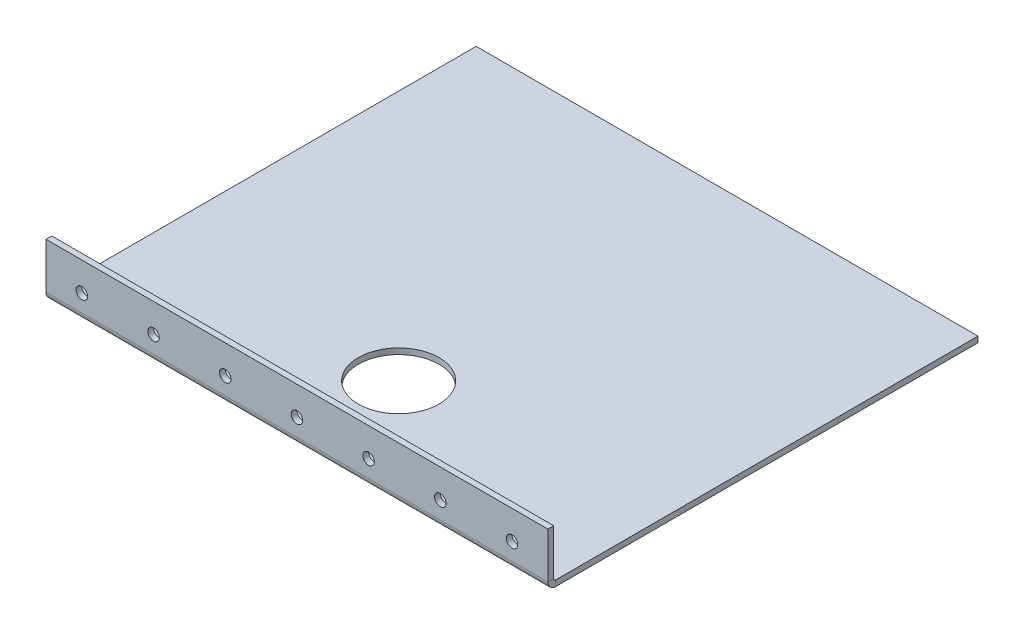
SolidWorks part; units mm, degrees
note: The reader was unsure of these and kept them because the rebuilt part matched: flange length of "Edge-Flange1".
ref_plane "Front Plane" through (0, 0, 0) normal (0, 0, 1) x (1, 0, 0)
ref_plane "Top Plane" through (0, 0, 0) normal (0, 1, 0) x (1, 0, 0)
ref_plane "Right Plane" through (0, 0, 0) normal (1, 0, 0) x (0, 0, -1)
sketch "Sketch1" plane through (0, 0, 0) normal (0, 1, 0) x (1, 0, 0)
  line L1 (-5638.8, 2754.0857) -> (-5461, 2754.0857)
  line L2 (-5638.8, 2754.0857) -> (-5638.8, 2601.6857)
  line L3 (-5638.8, 2601.6857) -> (-5461, 2601.6857)
  line L4 (-5461, 2754.0857) -> (-5461, 2601.6857)
  dimension "D1" = 152.4
  dimension "D2" = 177.8
base flange "Base-Flange1" sketch "Sketch1" thickness 2.0523 reverse thickness direction no parameters "D1"=0.7366
edge flange "Edge-Flange1" sketch "Sketch8" flange angle 90 flange length 19.05 flange position material inside bend radius 0.7366 thickness 2.0523 relief rectangular parameters "D6"=10
sketch "Sketch8" plane through (0, 0, -2601.6857) normal (0, 0, 1) x (1, 0, 0)
  line L2 (-5638.8, 0) -> (-5638.8, 16.9977)
  line L3 (-5638.8, 16.9977) -> (-5461, 16.9977)
  line L4 (-5461, 16.9977) -> (-5461, 0)
  line L5 (-5638.8, 0) -> (-5461, 0) construction
  line L6 (-5638.8, 0) -> (-5461, 0)
bend "EdgeBend1" bend radius 0.7366 bend angle 90 parameters "D5"=1
sketch "Sketch9" plane through (0, 0, -2603.738) normal (0, 0, -1) x (-1, 0, 0)
  line L0 (5461, 16.9977) -> (5638.8, 16.9977) construction
  line L1 (5638.8, 16.9977) -> (5638.8, 0.7366) construction
  circle A0 centre (5626.1, 6.8377) radius 2.032
  circle A1 centre (5600.7, 6.8377) radius 2.032
  circle A2 centre (5575.3, 6.8377) radius 2.032
  circle A3 centre (5549.9, 6.8377) radius 2.032
  circle A4 centre (5524.5, 6.8377) radius 2.032
  circle A5 centre (5499.1, 6.8377) radius 2.032
  circle A6 centre (5473.7, 6.8377) radius 2.032
  dimension "D1" = 4.064
  dimension "D2" = 10.16
  dimension "D3" = 12.7
  dimension "D4" = 7
extrude "Cut-Extrude1" cut sketch "Sketch9" against normal blind 2.54 normal cut yes
sketch "Sketch10" plane through (0, -2.0523, 0) normal (0, -1, 0) x (1, 0, 0)
  line L0 (-5461, -2601.6857) -> (-5638.8, -2601.6857) construction
  line L1 (-5461, -2604.4746) -> (-5461, -2754.0857) construction
  line L2 (-5638.8, -2754.0857) -> (-5638.8, -2604.4746) construction
  circle A0 centre (-5549.9, -2637.7334) radius 14.2875
  dimension "D1" = 28.575
  dimension "D3" = 88.9
  dimension "D4" = 88.9
  dimension "D2" = 36.0477
extrude "Cut-Extrude2" cut sketch "Sketch10" against normal blind 2.54 normal cut yes
sketch "Bend-Lines1" plane through (0, 0, 0) normal (0, 1, 0) x (1, 0, 0)
sketch "Bounding-Box1" plane through (0, 0, 0) normal (0, 1, 0) x (1, 0, 0)
sheet metal parameters "Sheet-Metal1" thickness 2.0523 parameters "D1"=0.7366
flat pattern "Flat-Pattern1" [suppressed]
sketch "Bend-Lines2" plane through (0, 0, 0) normal (0, 1, 0) x (1, 0, 0)
sketch "Bounding-Box2" [suppressed] plane through (0, 0, 0) normal (0, 1, 0) x (1, 0, 0)
sheet metal parameters "Sheet-Metal2" thickness 2.0523 parameters "D1"=0.7366
flat pattern "Flat-Pattern1" [suppressed]
sketch "Bend-Lines2" plane through (0, 0, 0) normal (0, 1, 0) x (1, 0, 0)
sketch "Bounding-Box2" [suppressed] plane through (0, 0, 0) normal (0, 1, 0) x (1, 0, 0)
bend of the flat pattern "Flatten-<EdgeBend1>1"
sheet metal parameters "Sheet-Metal3" thickness 2.0523 parameters "D1"=0.7366
flat pattern "Flat-Pattern1" [suppressed]
sketch "Bend-Lines2" plane through (0, 0, 0) normal (0, 1, 0) x (1, 0, 0)
sketch "Bounding-Box2" [suppressed] plane through (0, 0, 0) normal (0, 1, 0) x (1, 0, 0)
bend of the flat pattern "Flatten-<EdgeBend1>1"
sheet metal parameters "Sheet-Metal4" thickness 2.0523 parameters "D1"=0.7366
flat pattern "Flat-Pattern1" [suppressed]
sketch "Bend-Lines2" plane through (0, 0, 0) normal (0, 1, 0) x (1, 0, 0)
sketch "Bounding-Box2" [suppressed] plane through (0, 0, 0) normal (0, 1, 0) x (1, 0, 0)
bend of the flat pattern "Flatten-<EdgeBend1>1"
